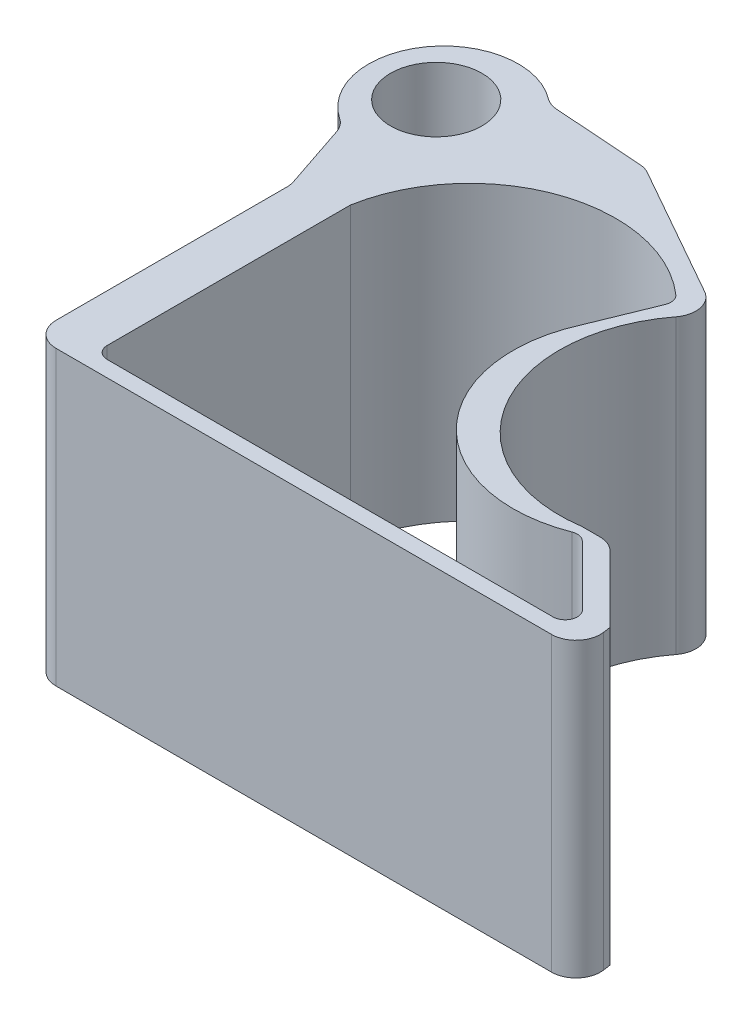
SolidWorks part; units mm, degrees
material "Markforged"
ref_plane "Front Plane" through (0, 0, 0) normal (0, 0, 1) x (1, 0, 0)
ref_plane "Top Plane" through (0, 0, 0) normal (0, 1, 0) x (1, 0, 0)
ref_plane "Right Plane" through (0, 0, 0) normal (1, 0, 0) x (0, 0, -1)
sketch "Sketch1" plane through (0, 0, 0) normal (0, 1, 0) x (1, 0, 0)
  line L0 (35.7754, 8.3677) -> (41.9881, 2.169)
  line L1 (41.0911, 0) -> (-5.3679, 0)
  line L2 (-6.6379, 1.27) -> (-6.6379, 26.6076)
  line L3 (16.2027, 27.8014) -> (18.7462, 34.0462)
  line L4 (5.3779, 45.3101) -> (22.4512, 35.6651)
  line L5 (5.3779, 45.3101) -> (-5.3679, 46.0642)
  line L6 (-14.2804, 33.4227) -> (-11.5757, 25.3612)
  line L7 (-11.5757, -1.6566) -> (45.5152, -1.6566)
  line L8 (45.0059, 2.0277) -> (37.3679, 9.6657)
  line L9 (-11.5757, 25.3612) -> (-11.5757, -1.6566)
  arc A0 (-6.6379, 26.6076) -> (18.4057, 35.4816) centre (8.3782, 24.0052) cw
  arc A1 (18.4057, 35.4816) -> (18.7462, 34.0462) centre (17.5701, 34.5253) cw
  arc A2 (-6.6379, 1.27) -> (-5.3679, 0) centre (-5.3679, 1.27) ccw
  arc A3 (41.9881, 2.169) -> (41.0911, 0) centre (41.0911, 1.27) cw
  arc A4 (34.4186, 8.6526) -> (35.7754, 8.3677) centre (34.8784, 7.4687) cw
  arc A5 (16.2027, 27.8014) -> (34.4186, 8.6526) centre (29.2464, 21.971) ccw
  circle A6 centre (-11.6788, 40.5984) radius 4.7625
  arc A7 (-14.2804, 33.4227) -> (-5.3679, 46.0642) centre (-10.6285, 40.3105) cw
  arc A8 (22.4512, 35.6651) -> (34.4325, 9.6657) centre (32.2505, 24.4206) ccw
  line B0 (22.4512, 35.6651) -> (5.3779, 45.3101)
  line B1 (34.4325, 9.6657) -> (37.3679, 9.6657)
  line B2 (37.3679, 9.6657) -> (45.0059, 2.0277)
  line B3 (45.0059, 2.0277) -> (45.5152, -1.6566)
  line B4 (45.5152, -1.6566) -> (-11.5757, -1.6566)
  line B5 (-11.5757, -1.6566) -> (-11.5757, 25.3612)
  line B6 (16.2027, 27.8014) -> (18.7462, 34.0462)
  line B7 (-6.6379, 26.6076) -> (-6.6379, 1.27)
  line B8 (-5.3679, 0) -> (41.0911, 0)
  line B9 (-11.5757, 25.3612) -> (-14.2804, 33.4227)
  line B10 (5.3779, 45.3101) -> (-5.3679, 46.0642)
  arc B11 (22.4512, 35.6651) -> (34.4325, 9.6657) centre (32.2505, 24.4206) ccw
  circle B12 centre (-11.6788, 40.5984) radius 4.7625
  arc B13 (18.7462, 34.0462) -> (18.4057, 35.4816) centre (17.5701, 34.5253) ccw
  arc B14 (18.4057, 35.4816) -> (-6.6379, 26.6076) centre (8.3782, 24.0052) ccw
  arc B15 (-6.6379, 1.27) -> (-5.3679, 0) centre (-5.3679, 1.27) ccw
  arc B16 (41.0911, 0) -> (41.9881, 2.169) centre (41.0911, 1.27) ccw
  arc B17 (34.4186, 8.6526) -> (35.7754, 8.3677) centre (34.8784, 7.4687) cw
  arc B18 (16.2027, 27.8014) -> (34.4186, 8.6526) centre (29.2464, 21.971) ccw
  arc B19 (-14.2804, 33.4227) -> (-5.3679, 46.0642) centre (-10.6285, 40.3105) cw
sketch_block_instance "Helper for Uprights-1"
sketch_block "Helper for Uprights"
extrude "Boss-Extrude2" add sketch "Sketch1" along normal blind 30.48 contours B3 L8 B1 A8 L4 L5 A7 L6 L9 L7 A6 L3 A5 A4 L0 A3 L1 A2 L2 A0 A1 region at (13.516, 0, -39.7821)
fillet "Fillet1" radius 2.54 8 edges at (5.3779, 15.24, -45.3101) (-5.3679, 15.24, -46.0642) (-14.2804, 15.24, -33.4227) (-11.5757, 15.24, -25.3612) (-11.5757, 15.24, 1.6566) (45.5152, 15.24, 1.6566) (37.3679, 15.24, -9.6657) (22.4512, 15.24, -35.6651)
